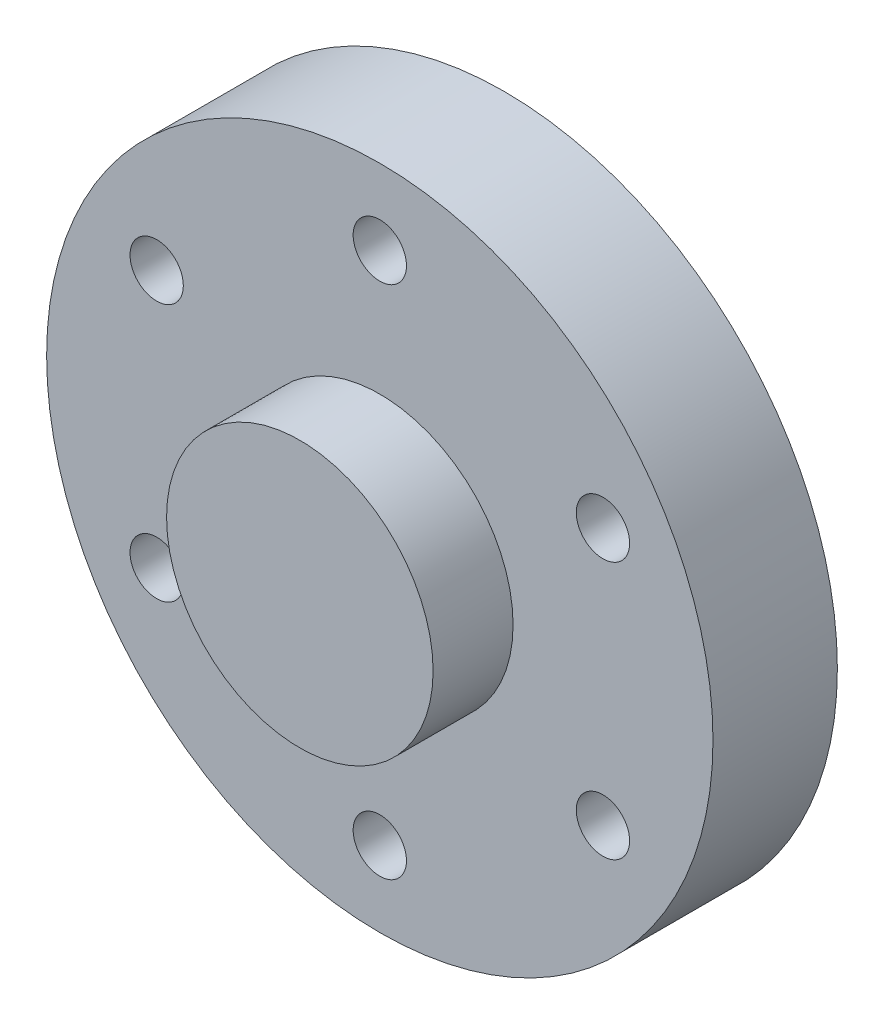
SolidWorks part; units mm, degrees
ref_plane "Front Plane" through (0, 0, 0) normal (0, 0, 1) x (1, 0, 0)
ref_plane "Top Plane" through (0, 0, 0) normal (0, 1, 0) x (1, 0, 0)
ref_plane "Right Plane" through (0, 0, 0) normal (1, 0, 0) x (0, 0, -1)
sketch "Sketch2" plane through (0, 0, 0) normal (0, 0, 1) x (1, 0, 0)
  circle A0 centre (0, 0) radius 9.5
  circle A1 centre (0, 0) radius 14.5 construction
  circle A3 centre (0, 0) radius 18.75
  circle A4 centre (0, 14.5) radius 1.5
  circle A5 centre (12.5574, 7.25) radius 1.5
  circle A6 centre (12.5574, -7.25) radius 1.5
  circle A7 centre (0, -14.5) radius 1.5
  circle A8 centre (-12.5574, -7.25) radius 1.5
  circle A9 centre (-12.5574, 7.25) radius 1.5
  point P21 (0, 0)
  dimension "D1" = 19
  dimension "D3" = 29
  dimension "D4" = 37.5
  dimension "D5" = 3
  dimension "D6" = 6
extrude "Boss-Extrude1" add sketch "Sketch2" along normal blind 7 contours A3 A9 A8 A7 A6 A5 A4 A0 | A0 region at (0, 0, 0) region at (-18.2197, 0, 0)
sketch "Sketch3" plane through (0, 0, 7) normal (0, 0, 1) x (1, 0, 0)
  circle A0 centre (0, 0) radius 7.5
  dimension "D1" = 15
extrude "Boss-Extrude2" add sketch "Sketch3" along normal blind 4.5
sketch "Sketch6" plane through (0, 0, 0) normal (0, 0, -1) x (-1, 0, 0)
  circle A0 centre (0, 0) radius 7.5
  dimension "D1" = 15
extrude "Boss-Extrude4" add sketch "Sketch6" along normal blind 4.5 contours A0
sketch "Sketch7" plane through (0, 0, -4.5) normal (0, 0, -1) x (-1, 0, 0)
  circle A0 centre (0, 0) radius 1.75
  dimension "D1" = 3.5
extrude "Boss-Extrude5" add sketch "Sketch7" along normal blind 1
fillet "Fillet2" radius 0.05 1 edges at (-1.75, 0, -5.5)
sketch "Sketch9" plane through (0, 0, -5.5) normal (0, 0, -1) x (-1, 0, 0)
  circle A0 centre (0, 0) radius 1.4
  dimension "D1" = 2.8
extrude "Cut-Extrude1" cut sketch "Sketch9" against normal blind 10
